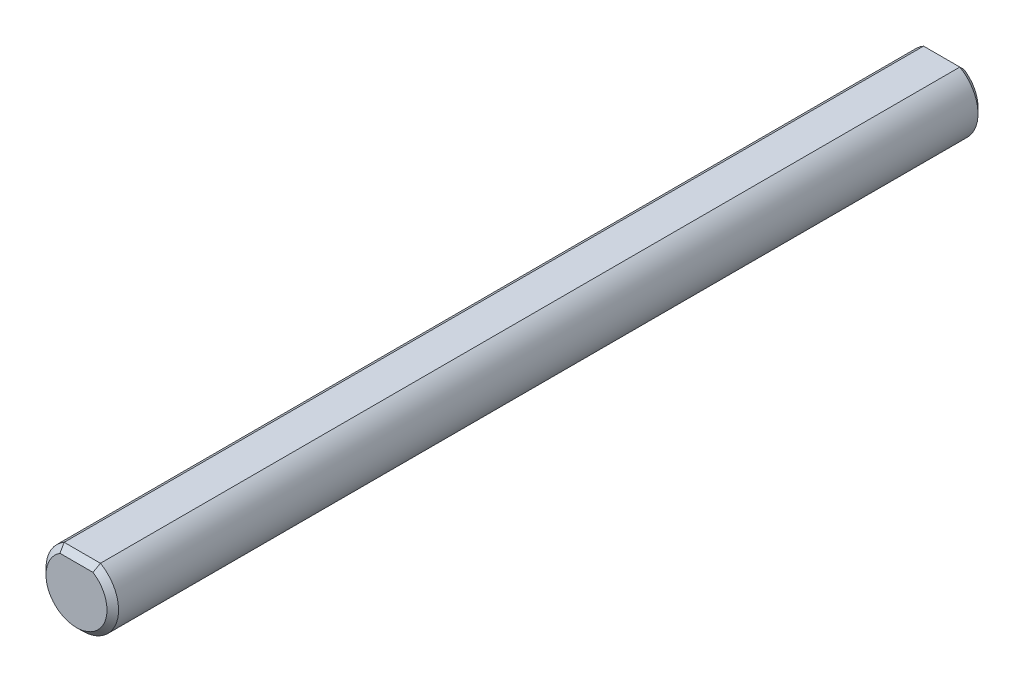
SolidWorks part; units mm, degrees
ref_plane "Front Plane" through (0, 0, 0) normal (0, 0, 1) x (1, 0, 0)
ref_plane "Top Plane" through (0, 0, 0) normal (0, 1, 0) x (1, 0, 0)
ref_plane "Right Plane" through (0, 0, 0) normal (1, 0, 0) x (0, 0, -1)
sketch "Sketch1" plane through (0, 0, 0) normal (0, 0, 1) x (1, 0, 0)
  line L0 (-1.5875, 2.7496) -> (1.5875, 2.7496)
  arc A0 (-1.5875, 2.7496) -> (1.5875, 2.7496) centre (0, 0) ccw
  dimension "D1" = 6.35
  dimension "D2" = 3.175
extrude "Boss-Extrude1" add sketch "Sketch1" along normal blind 76.2
chamfer "Chamfer1" distance 0.508 angle 45 4 edges at (0, 2.7496, 76.2) (0, -3.175, 76.2) (0, 2.7496, 0) (0, -3.175, 0)
